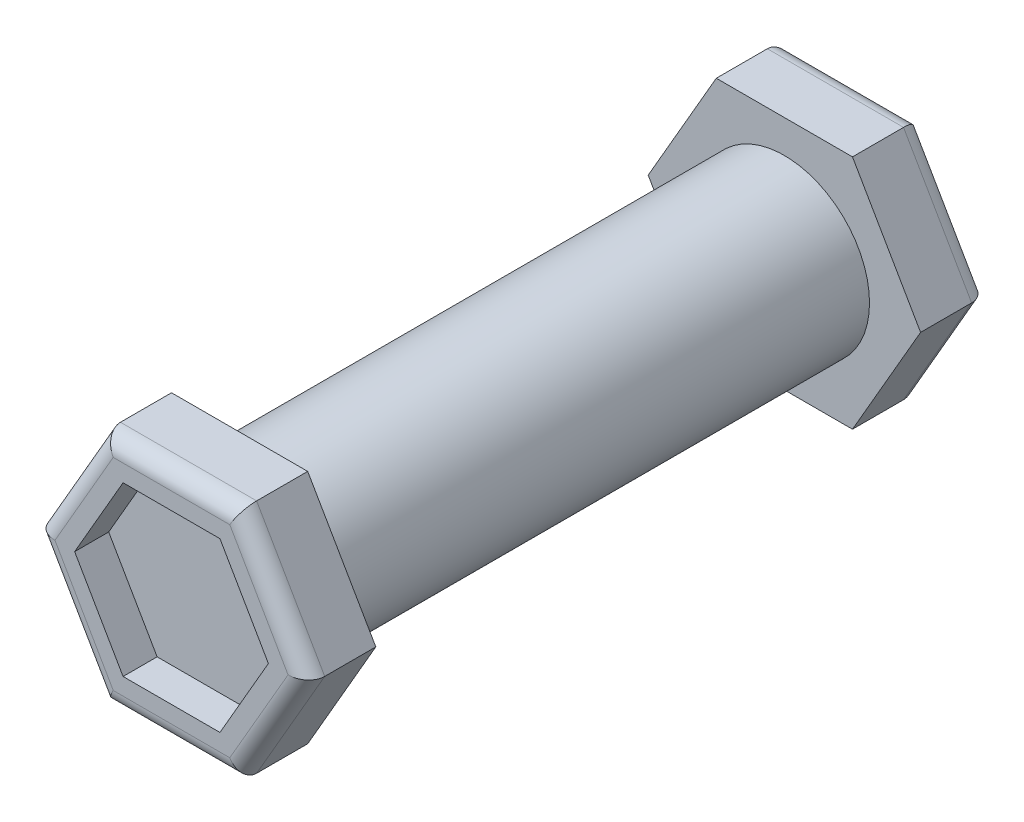
SolidWorks part; units mm, degrees
ref_plane "Front Plane" through (0, 0, 0) normal (0, 0, 1) x (1, 0, 0)
ref_plane "Top Plane" through (0, 0, 0) normal (0, 1, 0) x (1, 0, 0)
ref_plane "Right Plane" through (0, 0, 0) normal (1, 0, 0) x (0, 0, -1)
sketch "Sketch1" plane through (0, 0, 0) normal (0, 0, 1) x (1, 0, 0)
  circle A0 centre (0, 0) radius 0.625
  dimension "D1" = 1.25
extrude "Boss-Extrude1" add sketch "Sketch1" along normal blind 2 and the other way blind 2
sketch "Sketch2" plane through (0, 0, 2) normal (0, 0, 1) x (1, 0, 0)
  line L0 (-1, 0) -> (1, 0) construction
  line L1 (1, 0) -> (0.5, 0.866)
  line L2 (0.5, 0.866) -> (-0.5, 0.866)
  line L3 (-0.5, 0.866) -> (-1, 0)
  line L4 (-1, 0) -> (-0.5, -0.866)
  line L5 (-0.5, -0.866) -> (0.5, -0.866)
  line L6 (0.5, -0.866) -> (1, 0)
  circle A0 centre (0, 0) radius 0.866 construction
  dimension "D1" = 1
extrude "Boss-Extrude2" add sketch "Sketch2" along normal blind 0.5
fillet "Fillet1" radius 0.125 6 edges at (0, -0.866, 2.5) (-0.75, -0.433, 2.5) (-0.75, 0.433, 2.5) (0, 0.866, 2.5) (0.75, 0.433, 2.5) (0.75, -0.433, 2.5)
sketch "Sketch6" plane through (0, 0, 2.5) normal (0, 0, 1) x (1, 0, 0)
  line L12 (-0.7113, 0) -> (-0.3557, -0.616)
  line L13 (-0.3557, -0.616) -> (0.3557, -0.616)
  line L14 (0.3557, -0.616) -> (0.7113, 0)
  line L15 (0.7113, 0) -> (0.3557, 0.616)
  line L16 (0.3557, 0.616) -> (-0.3557, 0.616)
  line L17 (-0.3557, 0.616) -> (-0.7113, 0)
  line L18 (-0.7113, 0) -> (-0.3557, -0.616)
  line L19 (-0.3557, -0.616) -> (0.3557, -0.616)
  line L20 (0.3557, -0.616) -> (0.7113, 0)
  line L21 (0.7113, 0) -> (0.3557, 0.616)
  line L22 (0.3557, 0.616) -> (-0.3557, 0.616)
  line L23 (-0.3557, 0.616) -> (-0.7113, 0)
  dimension "D1" = 0.125
extrude "Cut-Extrude2" cut sketch "Sketch6" against normal blind 0.25
mirror "Mirror1" about plane through (0, 0, 0) normal (0, 0, 1) of "Fillet1", "Boss-Extrude2", "Cut-Extrude2"
scale "Scale1" scale about centroid uniform scaling yes scale factor 6
